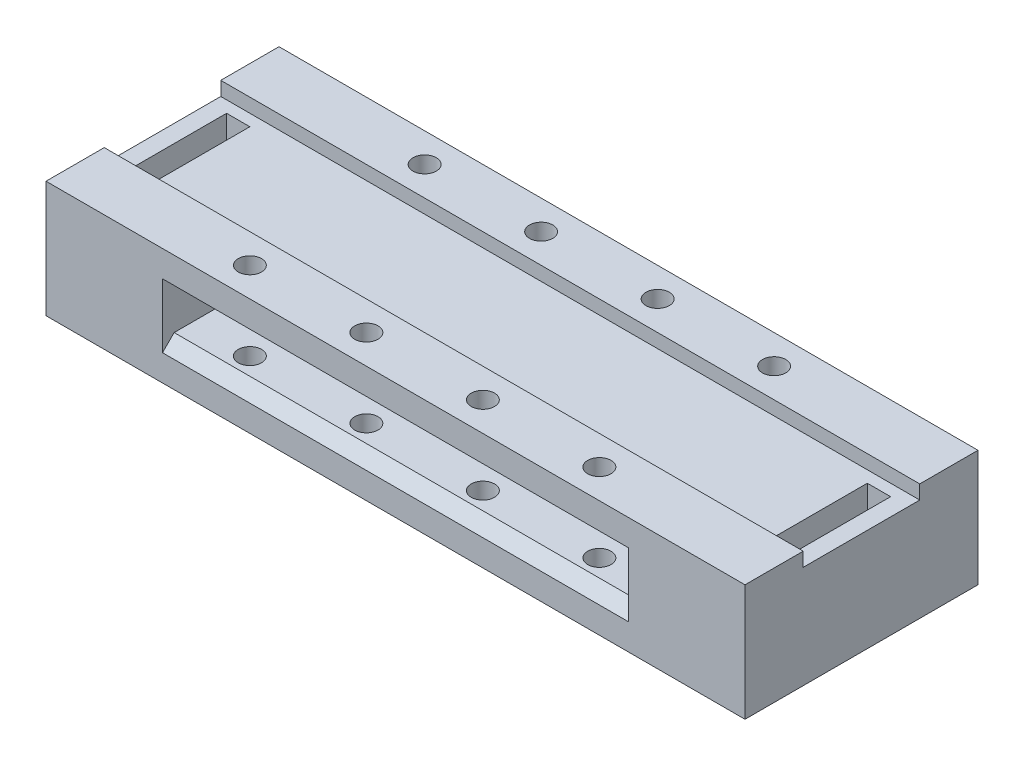
SolidWorks part; units mm, degrees
ref_plane "Front Plane" through (0, 0, 0) normal (0, 0, 1) x (1, 0, 0)
ref_plane "Top Plane" through (0, 0, 0) normal (0, 1, 0) x (1, 0, 0)
ref_plane "Right Plane" through (0, 0, 0) normal (1, 0, 0) x (0, 0, -1)
sketch "Sketch1" plane through (0, 0, 0) normal (0, 1, 0) x (1, 0, 0)
  line L1 (-30, -10) -> (30, -10)
  line L2 (-30, -10) -> (-30, 10)
  line L3 (-30, 10) -> (30, 10)
  line L4 (30, -10) -> (30, 10)
  line L5 (-30, -10) -> (30, 10) construction
  line L6 (-30, 10) -> (30, -10) construction
  point P0 (0, 0)
  dimension "D1" = 60
  dimension "D2" = 20
extrude "Base" add sketch "Sketch1" along normal blind 10
sketch "Sketch2" plane through (0, 0, 0) normal (0, -1, 0) x (1, 0, 0)
  circle A0 centre (-10, 0) radius 3.81
  dimension "D1" = 10
  dimension "D2" = 7.62
extrude "FSR Mount" add sketch "Sketch2" along normal blind 2
chamfer "Chamfer1" distance 2 angle 45 1 edges at (-10, 0, -3.81)
mirror "Mirror1" about plane through (0, 0, 0) normal (1, 0, 0) of "Chamfer1", "FSR Mount"
sketch "Sketch5" plane through (0, 0, -10) normal (0, 0, -1) x (-1, 0, 0)
  line L1 (20, 6.75) -> (-20, 6.75)
  line L2 (20, 6.75) -> (20, 3.25)
  line L3 (20, 3.25) -> (-20, 3.25)
  line L4 (-20, 6.75) -> (-20, 3.25)
  line L5 (20, 6.75) -> (-20, 3.25) construction
  line L6 (20, 3.25) -> (-20, 6.75) construction
  line L10 (-30, 5) -> (30, 5) construction
  line L11 (-30, 10) -> (-30, 0) construction
  line L12 (30, 10) -> (30, 0) construction
  point P0 (0, 5)
  dimension "D2" = 3.5
  dimension "D3" = 40
extrude "Cut-Extrude3" cut sketch "Sketch5" against normal up to surface (20 mm away) up to face at (0, 5, 10)
sketch "Sketch6" plane through (0, 3.25, 0) normal (0, 1, 0) x (1, 0, 0)
  line L0 (-20, -10) -> (-20, 10) construction
  line L1 (-20, -2.5) -> (20, -2.5)
  line L2 (-20, -2.5) -> (-20, 2.5)
  line L3 (-20, 2.5) -> (20, 2.5)
  line L4 (20, -2.5) -> (20, 2.5)
  line L5 (-20, -2.5) -> (20, 2.5) construction
  line L6 (-20, 2.5) -> (20, -2.5) construction
  line L7 (20, -10) -> (20, 10) construction
  point P0 (0, 0)
  dimension "D1" = 5
extrude "Boss-Extrude4" add sketch "Sketch6" along normal blind 1
sketch "Sketch8" plane through (0, 6.75, 0) normal (0, -1, 0) x (1, 0, 0)
  line L0 (-20, 10) -> (-20, 2.5) construction
  line L1 (-20, 2.5) -> (20, 2.5)
  line L2 (-20, 2.5) -> (-20, -2.5)
  line L3 (-20, -2.5) -> (20, -2.5)
  line L4 (20, 2.5) -> (20, -2.5)
  line L5 (-20, 2.5) -> (20, -2.5) construction
  line L6 (-20, -2.5) -> (20, 2.5) construction
  line L7 (-20, 2.5) -> (20, 2.5) construction
  point P0 (0, 0)
extrude "Cut-Extrude6" cut sketch "Sketch8" against normal offset from surface (1 mm away) 3.5 up to face at (0, 4.25, 0) offset beyond the face yes
chamfer "Chamfer2" distance 1 angle 45 8 edges at (0, 6.75, -2.5) (0, 6.75, 10) (0, 3.25, -2.5) (0, 3.25, 2.5) (0, 3.25, -10) (0, 6.75, -10) (0, 3.25, 10) (0, 6.75, 2.5)
sketch "Sketch9" plane through (0, 0, 0) normal (0, -1, 0) x (1, 0, 0)
  line L0 (-30, -10) -> (-30, 10) construction
  line L1 (-28.5, -4) -> (-26.5, -4)
  line L2 (-28.5, -4) -> (-28.5, 4)
  line L3 (-28.5, 4) -> (-26.5, 4)
  line L4 (-26.5, -4) -> (-26.5, 4)
  line L5 (-28.5, -4) -> (-26.5, 4) construction
  line L6 (-28.5, 4) -> (-26.5, -4) construction
  point P0 (-27.5, 0)
  dimension "D1" = 2
  dimension "D2" = 8
  dimension "D3" = 1.5
extrude "Cut-Extrude7" cut sketch "Sketch9" against normal up to surface (10 mm away) up to face at (0, 10, 0)
mirror "Mirror2" about plane through (0, 0, 0) normal (1, 0, 0) of "Cut-Extrude7"
sketch "Sketch10" plane through (0, 10, 0) normal (0, 1, 0) x (1, 0, 0)
  line L1 (30, -5) -> (-30, -5)
  line L2 (30, -5) -> (30, 5)
  line L3 (30, 5) -> (-30, 5)
  line L4 (-30, -5) -> (-30, 5)
  line L5 (30, -5) -> (-30, 5) construction
  line L6 (30, 5) -> (-30, -5) construction
  point P0 (0, 0)
  dimension "D2" = 10
  dimension "D3" = 60
extrude "Cut-Extrude8" cut sketch "Sketch10" against normal blind 1.2
sketch "Sketch11" plane through (0, 10, 0) normal (0, 1, 0) x (1, 0, 0)
  line L0 (-30, -7.5) -> (30, -7.5) construction
  line L1 (-30, -5) -> (-30, -10) construction
  line L2 (30, -10) -> (30, -5) construction
  circle A0 centre (-15, -7.5) radius 1
  circle A2 centre (-5, -7.5) radius 1
  circle A3 centre (5, -7.5) radius 1
  circle A4 centre (15, -7.5) radius 1
  dimension "D1" = 4
  dimension "D2" = 2
  dimension "D3" = 15
extrude "Cut-Extrude9" cut sketch "Sketch11" against normal through all
mirror "Mirror5" about plane through (0, 0, 0) normal (0, 0, 1) of "Cut-Extrude9"
